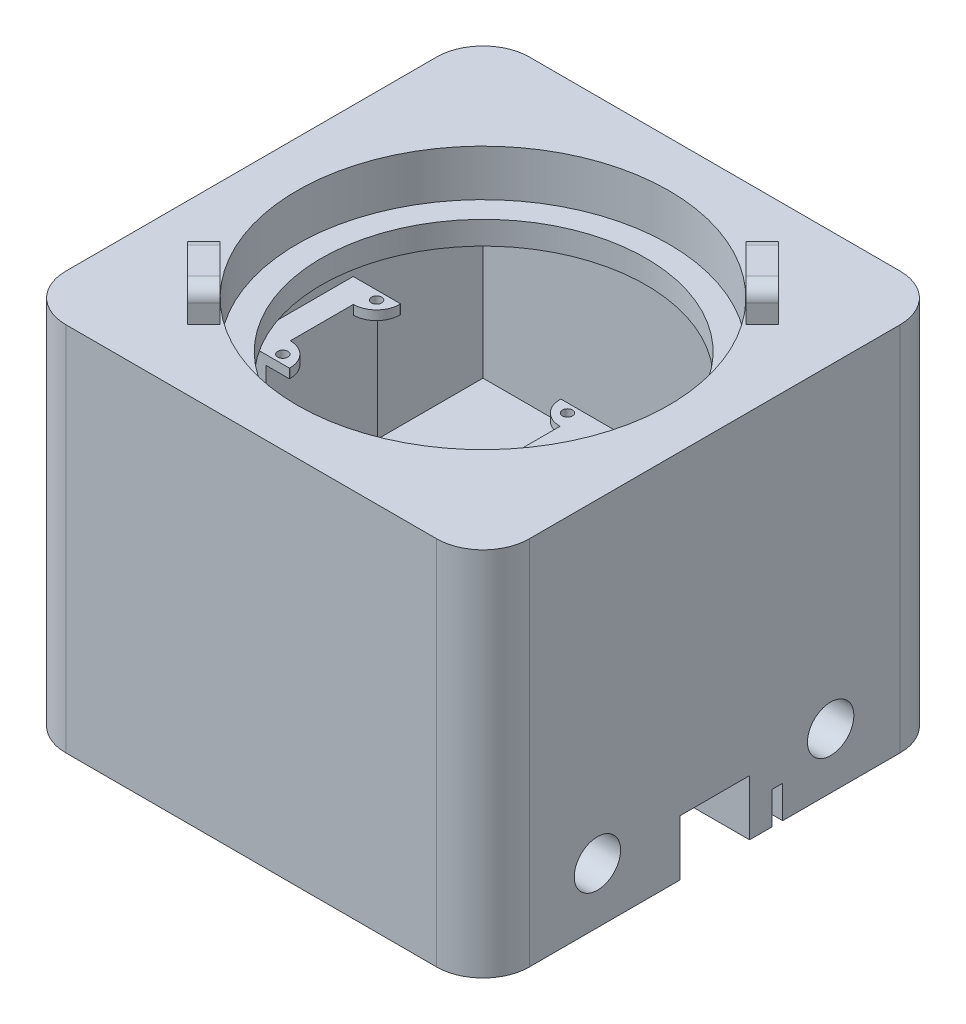
SolidWorks part; units mm, degrees
ref_plane "Front Plane" through (0, 0, 0) normal (0, 0, 1) x (1, 0, 0)
ref_plane "Top Plane" through (0, 0, 0) normal (0, 1, 0) x (1, 0, 0)
ref_plane "Right Plane" through (0, 0, 0) normal (1, 0, 0) x (0, 0, -1)
sketch "Sketch1" plane through (0, 0, 0) normal (0, 1, 0) x (1, 0, 0)
  line L1 (-50, 50) -> (50, 50)
  line L2 (-50, 50) -> (-50, -50)
  line L3 (-50, -50) -> (50, -50)
  line L4 (50, 50) -> (50, -50)
  line L5 (-50, 50) -> (50, -50) construction
  line L6 (-50, -50) -> (50, 50) construction
  point P0 (0, 0)
  dimension "D1" = 100
  dimension "D2" = 100
extrude "Boss-Extrude1" add sketch "Sketch1" along normal blind 25
sketch "Sketch2" plane through (0, 25, 0) normal (0, 1, 0) x (1, 0, 0)
  line L4 (40, 40) -> (-40, 40)
  line L5 (-40, 40) -> (-40, -40)
  line L6 (-40, -40) -> (40, -40)
  line L7 (40, -40) -> (40, 40)
  line L8 (50, -50) -> (50, 50)
  line L9 (50, 50) -> (-50, 50)
  line L10 (-50, 50) -> (-50, -50)
  line L11 (-50, -50) -> (50, -50)
  line L12 (50, -50) -> (50, 50)
  line L13 (50, 50) -> (-50, 50)
  line L14 (-50, 50) -> (-50, -50)
  line L15 (-50, -50) -> (50, -50)
  dimension "D1" = 0
  dimension "D2" = 10
extrude "Boss-Extrude2" add sketch "Sketch2" along normal blind 40 contours L4 L5 L6 L7 | L12 L13 L14 L15
sketch "Sketch3" plane through (-50, 0, 0) normal (-1, 0, 0) x (0, 0, 1)
  line L0 (-50, 0) -> (50, 0) construction
  line L2 (-7.5, 12) -> (7.5, 12)
  line L3 (-7.5, 12) -> (-7.5, 0)
  line L4 (-7.5, 0) -> (7.5, 0)
  line L5 (7.5, 12) -> (7.5, 0)
  line L6 (-7.5, 12) -> (7.5, 0) construction
  line L7 (-7.5, 0) -> (7.5, 12) construction
  circle A0 centre (-25, 12) radius 5
  circle A1 centre (25.3139, 12) radius 5
  point P6 (0, 0)
  point P7 (0, 6)
  dimension "D1" = 10
  dimension "D3" = 25
  dimension "D4" = 12
  dimension "D5" = 12
  dimension "D6" = 15
  dimension "D7" = 17.8139
  dimension "D8" = 7.5
  dimension "D9" = 0
  dimension "D2" = 2
extrude "Cut-Extrude1" cut sketch "Sketch3" against normal through all
sketch "Sketch4" plane through (0, 65, 0) normal (0, 1, 0) x (1, 0, 0)
  line L1 (-5.1, 47.1) -> (5.1, 47.1)
  line L2 (-5.1, 47.1) -> (-5.1, 42.9)
  line L3 (-5.1, 42.9) -> (5.1, 42.9)
  line L4 (5.1, 47.1) -> (5.1, 42.9)
  line L5 (-5.1, 47.1) -> (5.1, 42.9) construction
  line L6 (-5.1, 42.9) -> (5.1, 47.1) construction
  line L9 (10.1, 47.1) -> (10.1, 42.9)
  line L10 (10.1, 47.1) -> (20.3, 47.1)
  line L11 (20.3, 47.1) -> (20.3, 42.9)
  line L12 (10.1, 42.9) -> (20.3, 42.9)
  line L13 (25.3, 47.1) -> (25.3, 42.9)
  line L14 (25.3, 47.1) -> (35.5, 47.1)
  line L15 (35.5, 47.1) -> (35.5, 42.9)
  line L16 (25.3, 42.9) -> (35.5, 42.9)
  line L17 (-20.3, 47.1) -> (-20.3, 42.9)
  line L18 (-20.3, 47.1) -> (-10.1, 47.1)
  line L19 (-10.1, 47.1) -> (-10.1, 42.9)
  line L20 (-20.3, 42.9) -> (-10.1, 42.9)
  line L21 (-35.5, 47.1) -> (-35.5, 42.9)
  line L22 (-35.5, 47.1) -> (-25.3, 47.1)
  line L23 (-25.3, 47.1) -> (-25.3, 42.9)
  line L24 (-35.5, 42.9) -> (-25.3, 42.9)
  line L25 (0, 0) -> (60.9543, 0) construction
  line L26 (25.3, -47.1) -> (35.5, -47.1)
  line L27 (35.5, -47.1) -> (35.5, -42.9)
  line L28 (25.3, -42.9) -> (35.5, -42.9)
  line L29 (25.3, -47.1) -> (25.3, -42.9)
  line L30 (10.1, -47.1) -> (20.3, -47.1)
  line L31 (20.3, -47.1) -> (20.3, -42.9)
  line L32 (10.1, -42.9) -> (20.3, -42.9)
  line L33 (10.1, -47.1) -> (10.1, -42.9)
  line L34 (-5.1, -42.9) -> (5.1, -42.9)
  line L35 (5.1, -47.1) -> (5.1, -42.9)
  line L36 (-5.1, -47.1) -> (5.1, -47.1)
  line L37 (-5.1, -47.1) -> (-5.1, -42.9)
  line L38 (-35.5, -47.1) -> (-25.3, -47.1)
  line L39 (-25.3, -47.1) -> (-25.3, -42.9)
  line L40 (-35.5, -42.9) -> (-25.3, -42.9)
  line L41 (-35.5, -47.1) -> (-35.5, -42.9)
  line L42 (-20.3, -47.1) -> (-10.1, -47.1)
  line L43 (-10.1, -47.1) -> (-10.1, -42.9)
  line L44 (-20.3, -42.9) -> (-10.1, -42.9)
  line L45 (-20.3, -47.1) -> (-20.3, -42.9)
  line L64 (-47.1, 20.1) -> (-47.1, 9.9)
  line L65 (-47.1, 5.1) -> (-42.9, 5.1)
  line L66 (-47.1, 5.1) -> (-47.1, -5.1)
  line L67 (-47.1, -5.1) -> (-42.9, -5.1)
  line L68 (-42.9, 5.1) -> (-42.9, -5.1)
  line L69 (-47.1, 5.1) -> (-42.9, -5.1) construction
  line L70 (-47.1, -5.1) -> (-42.9, 5.1) construction
  line L71 (-47.1, 20.1) -> (-42.9, 20.1)
  line L72 (-42.9, 20.1) -> (-42.9, 9.9)
  line L73 (-47.1, 9.9) -> (-42.9, 9.9)
  line L74 (-47.1, 35.1) -> (-47.1, 24.9)
  line L75 (-47.1, 35.1) -> (-42.9, 35.1)
  line L76 (-42.9, 35.1) -> (-42.9, 24.9)
  line L77 (-47.1, 24.9) -> (-42.9, 24.9)
  line L78 (-47.1, 5.1) -> (-47.1, 20.1) construction
  line L79 (-47.1, -9.9) -> (-47.1, -20.1)
  line L80 (-47.1, -9.9) -> (-42.9, -9.9)
  line L81 (-42.9, -9.9) -> (-42.9, -20.1)
  line L82 (-47.1, -20.1) -> (-42.9, -20.1)
  line L83 (-47.1, -24.9) -> (-47.1, -35.1)
  line L84 (-47.1, -24.9) -> (-42.9, -24.9)
  line L85 (-42.9, -24.9) -> (-42.9, -35.1)
  line L86 (-47.1, -35.1) -> (-42.9, -35.1)
  line L87 (0, 0) -> (0, 14.7547) construction
  line L88 (47.1, -24.9) -> (42.9, -24.9)
  line L89 (42.9, -24.9) -> (42.9, -35.1)
  line L90 (47.1, -35.1) -> (42.9, -35.1)
  line L91 (47.1, -24.9) -> (47.1, -35.1)
  line L92 (47.1, -9.9) -> (42.9, -9.9)
  line L93 (42.9, -9.9) -> (42.9, -20.1)
  line L94 (47.1, -20.1) -> (42.9, -20.1)
  line L95 (47.1, -9.9) -> (47.1, -20.1)
  line L96 (47.1, -5.1) -> (42.9, -5.1)
  line L97 (42.9, 5.1) -> (42.9, -5.1)
  line L98 (47.1, 5.1) -> (42.9, 5.1)
  line L99 (47.1, 5.1) -> (47.1, -5.1)
  line L100 (47.1, 20.1) -> (42.9, 20.1)
  line L101 (42.9, 20.1) -> (42.9, 9.9)
  line L102 (47.1, 9.9) -> (42.9, 9.9)
  line L103 (47.1, 20.1) -> (47.1, 9.9)
  line L104 (47.1, 35.1) -> (42.9, 35.1)
  line L105 (42.9, 35.1) -> (42.9, 24.9)
  line L106 (47.1, 24.9) -> (42.9, 24.9)
  line L107 (47.1, 35.1) -> (47.1, 24.9)
  line L109 (50, 50) -> (-50, 50) construction
  line L110 (-50, 50) -> (-50, -50) construction
  point P0 (0, 45)
  point P46 (-45, 0)
  dimension "D1" = 4.2
  dimension "D2" = 5
  dimension "D3" = 3
  dimension "D5" = 5
  dimension "D6" = 10.2
  dimension "D7" = 0
  dimension "D8" = 5
  dimension "D9" = 4.2
  dimension "D10" = 10.2
  dimension "D11" = 0
  dimension "D13" = 15
  dimension "D15" = 5
  dimension "D4" = 3
  dimension "D12" = 3
  dimension "D14" = 3
extrude "Cut-Extrude2" [suppressed] cut sketch "Sketch4" against normal blind 10
fillet "Fillet2" radius 10 1 edges at (50, 32.5, 50) type face fillet first side face at (50, 12, -20) second side face at (0, 32.5, 50)
fillet "Fillet3" radius 10 1 edges at (50, 32.5, -50) type face fillet first side face at (50, 12, -20) second side face at (0, 32.5, -50)
fillet "Fillet4" radius 10 1 edges at (-50, 32.5, -50) type face fillet first side face at (-5, 32.5, -50) second side face at (-50, 12, -20)
fillet "Fillet5" radius 10 1 edges at (-50, 32.5, 50) type face fillet first side face at (-50, 12, -20) second side face at (-5, 32.5, 50)
sketch "Sketch5" plane through (0, 65, 0) normal (0, 1, 0) x (1, 0, 0)
  line L8 (-50, 40) -> (-50, -40)
  line L9 (-40, -50) -> (40, -50)
  line L10 (50, -40) -> (50, 40)
  line L11 (40, 50) -> (-40, 50)
  line L12 (-50, 40) -> (-50, -40)
  line L13 (-40, -50) -> (40, -50)
  line L14 (50, -40) -> (50, 40)
  line L15 (40, 50) -> (-40, 50)
  arc A8 (-50, -40) -> (-40, -50) centre (-40, -40) ccw
  arc A9 (40, -50) -> (50, -40) centre (40, -40) ccw
  arc A10 (50, 40) -> (40, 50) centre (40, 40) ccw
  arc A11 (-40, 50) -> (-50, 40) centre (-40, 40) ccw
  arc A12 (-50, -40) -> (-40, -50) centre (-40, -40) ccw
  arc A13 (40, -50) -> (50, -40) centre (40, -40) ccw
  arc A14 (50, 40) -> (40, 50) centre (40, 40) ccw
  arc A15 (-40, 50) -> (-50, 40) centre (-40, 40) ccw
  dimension "D1" = 0
extrude "Boss-Extrude3" add sketch "Sketch5" along normal blind 15
sketch "Sketch6" plane through (0, 80, 0) normal (0, 1, 0) x (1, 0, 0)
  line L5 (-23.357, -23.5) -> (23.643, -23.5) construction
  line L6 (-23.357, -23.5) -> (-23.357, 23.5) construction
  line L7 (-23.357, 23.5) -> (23.643, 23.5) construction
  line L8 (23.643, -23.5) -> (23.643, 23.5) construction
  line L9 (-23.357, -23.5) -> (23.643, 23.5) construction
  line L10 (-23.357, 23.5) -> (23.643, -23.5) construction
  circle A4 centre (0.143, 0) radius 35
  point P0 (0, 0)
  point P6 (23.643, 0)
  dimension "D3" = 47
  dimension "D1" = 70
  dimension "D2" = 47
  dimension "D4" = 0
extrude "Cut-Extrude3" cut sketch "Sketch6" against normal blind 25
sketch "Sketch7" plane through (0, 80, 0) normal (0, 1, 0) x (1, 0, 0)
  circle A0 centre (0, 0) radius 40.1
  dimension "D1" = 80.2
extrude "Cut-Extrude4" cut sketch "Sketch7" against normal blind 10
sketch "Sketch8" plane through (0, 25, 0) normal (0, 1, 0) x (1, 0, 0)
  circle A0 centre (0, 0) radius 7 construction
  dimension "D1" = 14
sketch "Sketch9" plane through (0, 0, 0) normal (0, 0, 1) x (1, 0, 0)
  line L0 (9.8, 56) -> (9.8, 25)
  line L1 (9.8, 25) -> (16.8, 25)
  line L2 (16.8, 25) -> (16.8, 58)
  line L3 (16.8, 58) -> (4.8, 58)
  line L4 (4.8, 58) -> (4.8, 56)
  line L5 (4.8, 56) -> (9.8, 56)
  line L6 (7, 25) -> (-7, 25) construction
  dimension "D1" = 2
  dimension "D2" = 31
  dimension "D3" = 12
  dimension "D4" = 5
  dimension "D5" = 0
  dimension "D6" = 9.8
extrude "Boss-Extrude4" add sketch "Sketch9" along normal blind 12 and the other way blind 12
ref_plane "Plane1" through (-12.485, 0, 0) normal (-1, 0, 0) x (0, 0, 1)
mirror "Mirror1" about plane through (-12.485, 0, 0) normal (-1, 0, 0) of "Boss-Extrude4"
sketch "Sketch10" plane through (0, 58, 0) normal (0, 1, 0) x (1, 0, 0)
  line L0 (16.8, -12) -> (4.8, -12) construction
  line L2 (16.8, 12) -> (4.8, 12) construction
  line L3 (4.8, 12) -> (4.8, -12) construction
  line L9 (4.8, -6.8) -> (9.8, -6.8)
  line L10 (4.8, -6.8) -> (4.8, 6.8)
  line L11 (4.8, 6.8) -> (9.8, 6.8)
  line L12 (9.8, -6.8) -> (9.8, 6.8)
  line L13 (16.8, 12) -> (16.8, -12) construction
  circle A0 centre (8.1, -10.125) radius 1.1
  circle A2 centre (8.1, 10.125) radius 1.1
  point P14 (9.8, 0)
  dimension "D1" = 2.2
  dimension "D3" = 1.875
  dimension "D5" = 1.875
  dimension "D9" = 8.7
  dimension "D2" = 2.2
  dimension "D4" = 20.25
  dimension "D6" = 13.6
  dimension "D7" = 12
  dimension "D8" = 5
extrude "Cut-Extrude5" cut sketch "Sketch10" against normal blind 10
mirror "Mirror2" about plane through (-12.485, 0, 0) normal (-1, 0, 0) of "Cut-Extrude5"
fillet "Fillet6" radius 5 4 edges at (-29.77, 57, 6.8) (-29.77, 57, -6.8) (4.8, 57, 6.8) (4.8, 57, -6.8)
sketch "Sketch11" plane through (0, 0, 12) normal (0, 0, 1) x (1, 0, 0)
  line L0 (16.8, 25) -> (16.8, 58) construction
  line L1 (4.8, 58) -> (16.8, 58)
  line L2 (4.8, 58) -> (4.8, 57.5)
  line L3 (4.8, 57.5) -> (16.8, 57.5)
  line L4 (16.8, 58) -> (16.8, 57.5)
  dimension "D1" = 0.5
extrude "Cut-Extrude6" cut sketch "Sketch11" against normal blind 24
sketch "Sketch12" plane through (0, 25, 0) normal (0, 1, 0) x (1, 0, 0)
  line L0 (-50, -7.5) -> (-50, 7.5) construction
  line L1 (-7, 7.5) -> (-17, 7.5)
  line L2 (-7, 7.5) -> (-7, -7.5)
  line L3 (-7, -7.5) -> (-17, -7.5)
  line L4 (-17, 7.5) -> (-17, -7.5)
  line L5 (-7, 7.5) -> (-17, -7.5) construction
  line L6 (-7, -7.5) -> (-17, 7.5) construction
  point P0 (-12, 0)
  point P7 (-7, 0)
  dimension "D1" = 15
  dimension "D2" = 33
  dimension "D3" = 10
  dimension "D4" = 0
extrude "Cut-Extrude7" cut sketch "Sketch12" against normal blind 24
sketch "Sketch15" plane through (0, 25, 0) normal (0, 1, 0) x (1, 0, 0)
  line L0 (-34.77, 12) -> (-34.77, -12) construction
  line L1 (-17.485, -12) -> (-7.485, -12)
  line L2 (-17.485, -12) -> (-17.485, -9.25)
  line L3 (-17.485, -9.25) -> (-7.485, -9.25)
  line L4 (-7.485, -12) -> (-7.485, -9.25)
  dimension "D1" = 2.75
  dimension "D2" = 10
  dimension "D3" = 17.285
extrude "Boss-Extrude5" add sketch "Sketch15" along normal blind 5.4
ref_plane "Plane2" through (0, 0, 0) normal (-0.7071, 0, -0.7071) x (-0.7071, 0, 0.7071)
sketch "Sketch18" plane through (0, 0, 0) normal (0, -1, 0) x (1, 0, 0)
  line L1 (-50, -40) -> (-50, -7.5) construction
  line L3 (-50, -12.35) -> (-50, -14.65)
  line L4 (50, -7.5) -> (-50, -7.5) construction
  line L5 (0, 0) -> (0, -31.8736) construction
  line L6 (41.8458, -14.65) -> (50, -14.65)
  line L7 (50, -12.35) -> (50, -14.65)
  line L8 (50, -12.35) -> (41.8458, -12.35)
  line L9 (-50, -12.35) -> (-41.8311, -12.35)
  line L10 (-50, -14.65) -> (-41.8311, -14.65)
  circle A0 centre (-38, -13.5) radius 2.5
  arc A2 (41.8458, -14.65) -> (41.8458, -12.35) centre (38, -13.5) cw
  circle A3 centre (38, -13.5) radius 2.5
  arc A4 (-41.8311, -14.65) -> (-41.8311, -12.35) centre (-38, -13.5) ccw
  point P11 (-50, -13.5)
  dimension "D1" = 6
  dimension "D2" = 12
  dimension "D3" = 2.3
  dimension "D4" = 8
  dimension "D5" = 1.5
  dimension "D6" = 6
  dimension "D7" = 2.3
extrude "Cut-Extrude8" cut sketch "Sketch18" against normal blind 7
ref_plane "Plane3" through (0, 0, 0) normal (-0.7071, 0, 0.7071) x (0.7071, 0, 0.7071)
ref_plane "Plane4" through (-28.355, 0, 28.355) normal (-0.7071, 0, 0.7071) x (0.7071, 0, 0.7071)
sketch "Sketch20" plane through (-28.355, 0, 28.355) normal (-0.7071, 0, 0.7071) x (0.7071, 0, 0.7071)
  line L0 (-4.4989, 80) -> (-4.4989, 84)
  line L1 (-7.0711, 80) -> (-4.4989, 80)
  line L2 (-7.0711, 80) -> (-7.0711, 87)
  line L3 (-7.0711, 87) -> (7.0711, 87)
  line L4 (7.0711, 80) -> (7.0711, 87)
  line L5 (-4.4989, 84) -> (4.5011, 84)
  line L6 (4.5011, 84) -> (4.5011, 80)
  line L7 (4.5011, 80) -> (7.0711, 80)
  dimension "D1" = 14.1421
  dimension "D2" = 7
  dimension "D3" = 9
  dimension "D4" = 4
  dimension "D5" = 2.57
extrude "Boss-Extrude6" add sketch "Sketch20" along normal blind 5
fillet "Fillet8" radius 3 2 edges at (-25.1227, 87, 35.1227) (-35.1227, 87, 25.1227)
mirror "Mirror3" about plane through (0, 0, 0) normal (-0.7071, 0, 0.7071) of "Fillet8", "Boss-Extrude6"
